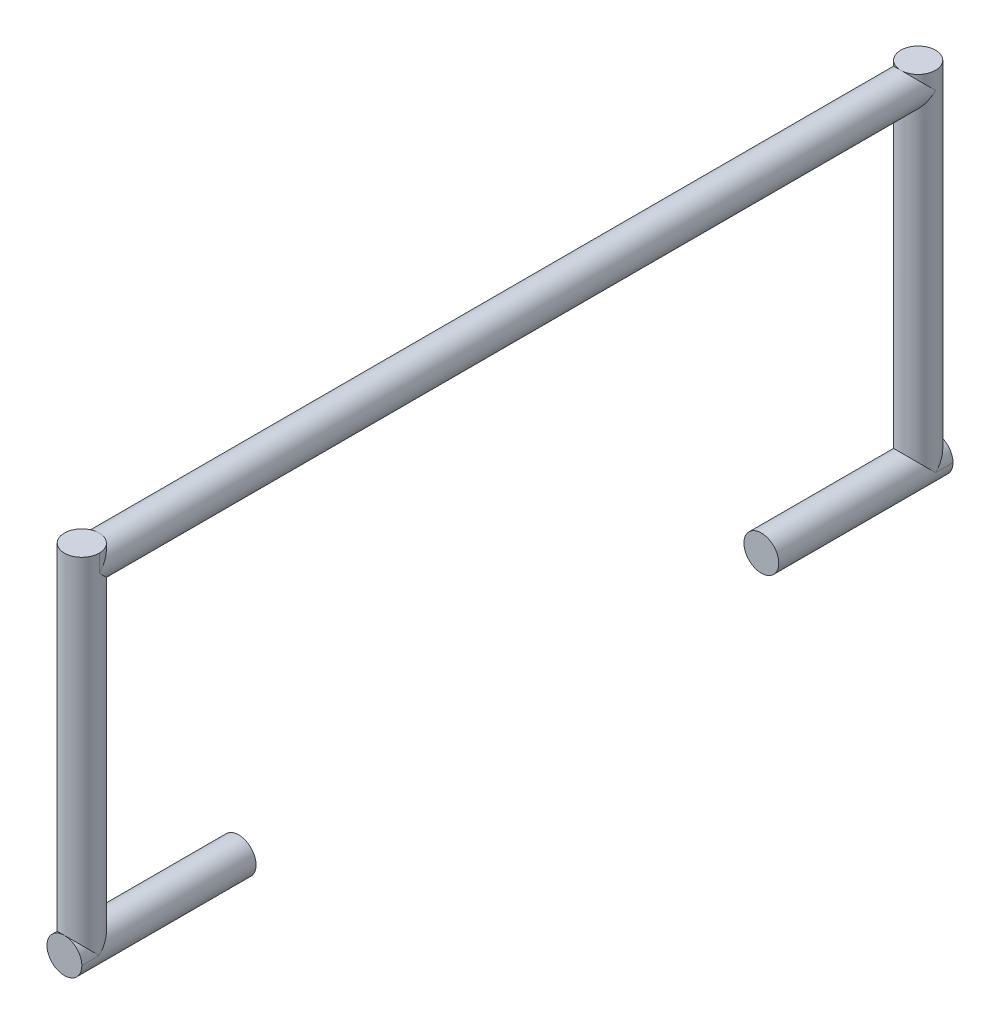
SolidWorks part; units mm, degrees
ref_plane "Front Plane" through (0, 0, 0) normal (0, 0, 1) x (1, 0, 0)
ref_plane "Top Plane" through (0, 0, 0) normal (0, 1, 0) x (1, 0, 0)
ref_plane "Right Plane" through (0, 0, 0) normal (1, 0, 0) x (0, 0, -1)
sketch "Sketch1" plane through (0, 0, 0) normal (0, 0, 1) x (1, 0, 0)
  circle A0 centre (0, 0) radius 0.635
  dimension "D1" = 1.27
extrude "Boss-Extrude1" add sketch "Sketch1" along normal mid plane 30.48
ref_plane "Plane4" through (0, 0.635, 0) normal (0, 1, 0) x (1, 0, 0)
sketch "Sketch2" plane through (0, 0.635, 0) normal (0, 1, 0) x (1, 0, 0)
  line L0 (-0.635, -15.24) -> (0.635, -15.24) construction
  circle A0 centre (0, -15.24) radius 0.635
  point P6 (0, 0)
  dimension "D1" = 1.27
extrude "Boss-Extrude2" add sketch "Sketch2" against normal blind 12.7
ref_plane "Plane5" through (0, 0, 15.875) normal (0, 0, 1) x (1, 0, 0)
sketch "Sketch3" plane through (0, 0, 15.875) normal (0, 0, 1) x (1, 0, 0)
  line L0 (-0.635, -12.065) -> (0.635, -12.065) construction
  circle A0 centre (0, -12.065) radius 0.635
extrude "Boss-Extrude3" add sketch "Sketch3" against normal blind 6.35
mirror "Mirror1" about plane through (0, 0, 0) normal (0, 0, 1) of "Boss-Extrude3", "Boss-Extrude2"
ref_point "Point1"
ref_axis "Axis1" through (0, 0, 0) along (0, 1, 0)
